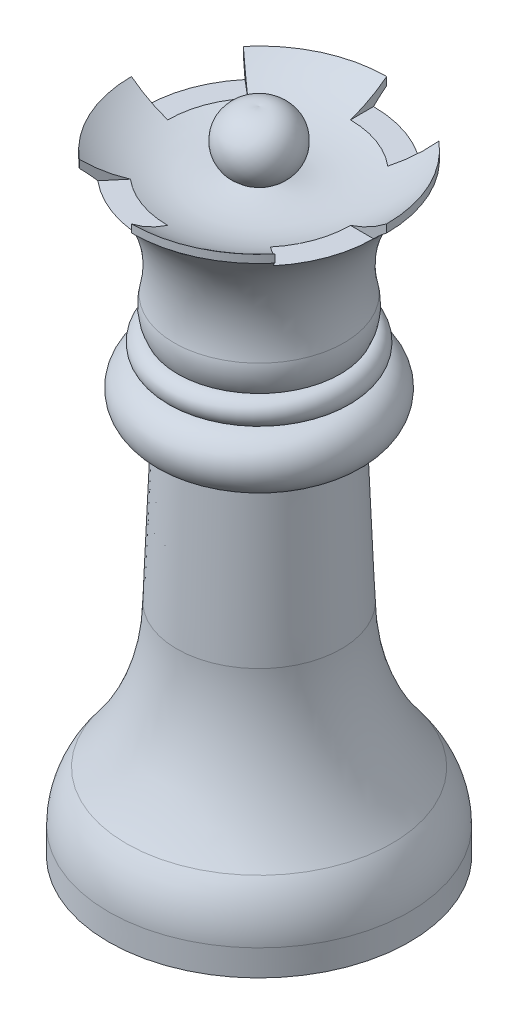
SolidWorks part; units mm, degrees
material "PVC Rigid"
ref_plane "Front Plane" through (0, 0, 0) normal (0, 0, 1) x (1, 0, 0)
ref_plane "Top Plane" through (0, 0, 0) normal (0, 1, 0) x (1, 0, 0)
ref_plane "Right Plane" through (0, 0, 0) normal (1, 0, 0) x (0, 0, -1)
sketch "Sketch1" plane through (0, 0, 0) normal (0, 0, 1) x (1, 0, 0)
  line L0 (0, 0) -> (-11.6, 0)
  line L3 (-11.5897, 2) -> (-11.6, 0)
  line L32 (0, 50) -> (0, 0)
  line L33 (-5.8734, 29.12) -> (-6.3432, 29.12)
  line L34 (-6.3432, 16.936) -> (-5.8734, 29.12)
  line L35 (-9.8373, 46.4466) -> (-9.8373, 47.061)
  line L36 (0, 0) -> (0, 50) construction
  arc A0 (-10.2296, 5.8838) -> (-11.5897, 2) centre (-5.271, 1.9673) ccw
  circle A32 centre (0, 47.5962) radius 2.4038 construction
  arc A34 (0, 50) -> (-1.2079, 45.5179) centre (-0.4218, 47.7099) ccw
  arc A36 (-6.3432, 29.12) -> (-6.2866, 33.2698) centre (-6.3432, 31.1953) cw
  arc A39 (-9.8373, 46.4466) -> (-6.5463, 37.467) centre (-15.0641, 39.4381) cw
  arc A40 (-10.2296, 5.8838) -> (-6.3432, 16.936) centre (-24.3998, 17.076) ccw
  arc A42 (-9.8373, 47.061) -> (-1.2079, 45.5179) centre (-4.0599, 54.4691) ccw
  arc A43 (-6.2866, 33.2698) -> (-6.2597, 35.24) centre (-6.2598, 34.2547) cw
  arc A44 (-6.5463, 37.467) -> (-6.2597, 35.24) centre (-3.4026, 36.7396) ccw
  dimension "D4" = 50
  dimension "D35" = 2.3287
  dimension "D1" = 2
  dimension "D5" = 11.6
revolve "Revolve6" add sketch "Sketch1" angle 360 about L32 region at (-3.8926, 21.7552, 0)
sketch "Sketch10" plane through (0, 0, 0) normal (0, 0, 1) x (1, 0, 0)
  line L0 (-9.8373, 48.8388) -> (-9.8373, 47.061) construction
  line L1 (-14.5937, 48.8388) -> (-5.0809, 48.8388)
  line L2 (-14.5937, 48.8388) -> (-14.5937, 45.561)
  line L3 (-14.5937, 45.561) -> (-5.0809, 45.561)
  line L4 (-5.0809, 48.8388) -> (-5.0809, 45.561)
  point P7 (-9.8373, 45.561)
  point P8 (-5.0809, 45.561)
  dimension "D1" = 1.5
revolve "Cut-Revolve8" cut sketch "Sketch10" angle 40 about L36 reverse direction yes
sketch "Sketch11" plane through (0, 0, 0) normal (0, 0, 1) x (1, 0, 0)
  line L0 (9.8373, 49.9649) -> (9.8373, 47.061) construction
  line L1 (6.3584, 49.9649) -> (13.3161, 49.9649)
  line L2 (6.3584, 49.9649) -> (6.3584, 45.561)
  line L3 (6.3584, 45.561) -> (13.3161, 45.561)
  line L4 (13.3161, 49.9649) -> (13.3161, 45.561)
  line L5 (-9.8373, 47.061) -> (9.8373, 47.061) construction
  dimension "D1" = 1.5
revolve "Cut-Revolve9" cut sketch "Sketch11" angle 40 about L36 reverse direction yes
sketch "Sketch12" plane through (0, 0, 0) normal (1, 0, 0) x (0, 0, -1)
  line L0 (9.8373, 48.8989) -> (9.8373, 47.061) construction
  line L1 (5.2356, 48.8989) -> (14.4389, 48.8989)
  line L2 (5.2356, 48.8989) -> (5.2356, 45.561)
  line L3 (5.2356, 45.561) -> (14.4389, 45.561)
  line L4 (14.4389, 48.8989) -> (14.4389, 45.561)
  line L5 (0, 47.061) -> (9.8373, 47.061) construction
  dimension "D1" = 1.5
revolve "Cut-Revolve10" cut sketch "Sketch12" angle 40 about L36 reverse direction yes
sketch "Sketch13" plane through (0, 0, 0) normal (1, 0, 0) x (0, 0, -1)
  line L0 (-9.8373, 48.6739) -> (-9.8373, 47.061) construction
  line L1 (-14.1563, 48.6739) -> (-5.5182, 48.6739)
  line L2 (-14.1563, 48.6739) -> (-14.1563, 45.561)
  line L3 (-14.1563, 45.561) -> (-5.5182, 45.561)
  line L4 (-5.5182, 48.6739) -> (-5.5182, 45.561)
  line L5 (0, 47.061) -> (-9.8373, 47.061) construction
  point P8 (-9.8373, 45.561)
  dimension "D1" = 1.5
revolve "Cut-Revolve11" cut sketch "Sketch13" angle 40 about L36 reverse direction yes
sketch "Sketch8" plane through (0, 0, 0) normal (0, -1, 0) x (1, 0, 0)
  circle A0 centre (0, 0) radius 10
extrude "Cut-Extrude1" cut sketch "Sketch8" against normal blind 2 from offset 0.4 offset against normal yes
